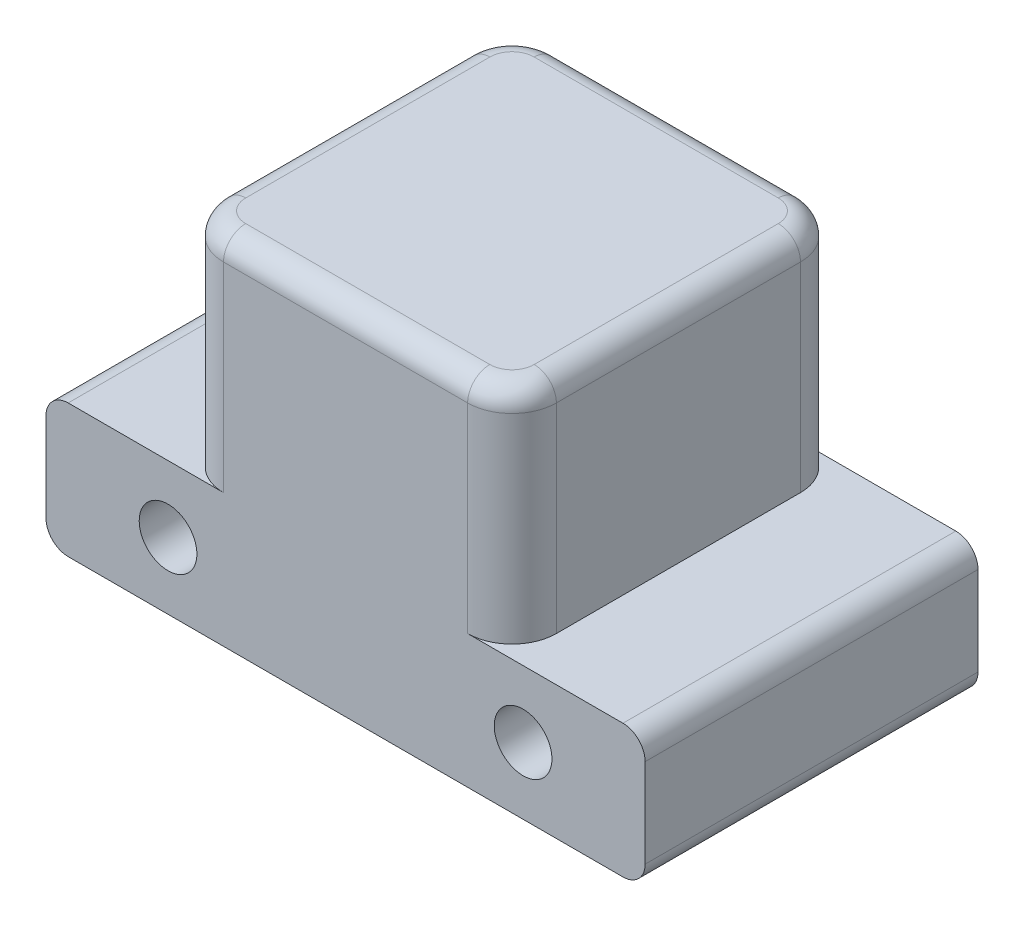
SolidWorks part; units mm, degrees
ref_plane "正面" through (0, 0, 0) normal (0, 0, 1) x (1, 0, 0)
ref_plane "平面" through (0, 0, 0) normal (0, 1, 0) x (1, 0, 0)
ref_plane "右側面" through (0, 0, 0) normal (1, 0, 0) x (0, 0, -1)
sketch "ｽｹｯﾁ1" plane through (0, 0, 0) normal (0, 0, 1) x (1, 0, 0)
  line L0 (0, 8) -> (0, 0) construction
  line L1 (-7.5, 8) -> (7.5, 8)
  line L2 (-7.5, 8) -> (-7.5, -2)
  line L3 (-7.5, -8) -> (7.5, -8)
  line L4 (7.5, 8) -> (7.5, -2)
  line L5 (-7.5, 8) -> (7.5, -8) construction
  line L6 (-7.5, -8) -> (7.5, 8) construction
  line L7 (7.5, -8) -> (13.5, -8)
  line L8 (7.5, -8) -> (7.5, -2) construction
  line L9 (7.5, -2) -> (13.5, -2)
  line L10 (13.5, -8) -> (13.5, -2)
  line L11 (-13.5, -8) -> (-13.5, -2)
  line L12 (-7.5, -2) -> (-13.5, -2)
  line L13 (-7.5, -8) -> (-7.5, -2) construction
  line L14 (-7.5, -8) -> (-13.5, -8)
  line L15 (-7.5, -2) -> (-7.5, -8) construction
  line L16 (7.5, -2) -> (7.5, -8) construction
  circle A0 centre (8, -5) radius 1.3
  circle A1 centre (-8, -5) radius 1.3
  point P0 (0, 0)
  dimension "D5" = 2.6
  dimension "D1" = 15
  dimension "D2" = 10
  dimension "D3" = 6
  dimension "D4" = 6
  dimension "D6" = 3
  dimension "D7" = 16
extrude "ﾎﾞｽ - 押し出し1" add sketch "ｽｹｯﾁ1" along normal blind 15
fillet "ﾌｨﾚｯﾄ1" radius 2 4 edges at (-7.5, 3, 0) (7.5, 3, 0) (7.5, 3, 15) (-7.5, 3, 15)
fillet "ﾌｨﾚｯﾄ3" radius 1 4 edges at (13.5, -8, 7.5) (13.5, -2, 7.5) (-13.5, -8, 7.5) (-13.5, -2, 7.5)
fillet "ﾌｨﾚｯﾄ4" radius 1 8 edges at (6.9142, 8, 14.4142) (7.5, 8, 7.5) (6.9142, 8, 0.5858) (0, 8, 0) (-6.9142, 8, 0.5858) (-7.5, 8, 7.5) (-6.9142, 8, 14.4142) (0, 8, 15)
ref_plane "平面1" through (0, 7, 0) normal (0, 1, 0) x (1, 0, 0)
sketch "ｽｹｯﾁ2" plane through (0, 7, 0) normal (0, 1, 0) x (1, 0, 0)
  line L0 (0, 0) -> (0, -15) construction
  line L1 (5.5, -15) -> (-5.5, -15) construction
  line L3 (-4.15, -3.35) -> (4.15, -3.35)
  line L4 (-4.15, -3.35) -> (-4.15, -11.65)
  line L5 (-4.15, -11.65) -> (4.15, -11.65)
  line L6 (4.15, -3.35) -> (4.15, -11.65)
  line L7 (-4.15, -3.35) -> (4.15, -11.65) construction
  line L8 (-4.15, -11.65) -> (4.15, -3.35) construction
  circle A1 centre (4.15, -3.35) radius 1
  circle A2 centre (4.15, -11.65) radius 1
  circle A3 centre (-4.15, -11.65) radius 1
  circle A4 centre (-4.15, -3.35) radius 1
  point P5 (0, -7.5)
  point P19 (0, -7.5)
  dimension "D1" = 8.3
  dimension "D2" = 2
  dimension "D3" = 4
extrude "ｶｯﾄ - 押し出し1" [suppressed] cut sketch "ｽｹｯﾁ2" against normal blind 2 contours L4 A3 L5 | L5 A2 L6 | L6 A1 L3 | L3 A4 L4 | A4 L4 A3 L5 A2 L6 A1 L3 | L4 A4 L3 | L3 A1 L6 | L6 A2 L5 | L5 A3 L4
sketch "ｽｹｯﾁ3" plane through (0, 7, 0) normal (0, 1, 0) x (1, 0, 0)
  line L0 (0, 0) -> (0, -15) construction
  line L1 (5.5, -15) -> (-5.5, -15) construction
  circle A0 centre (0, -7.5) radius 3.15
  dimension "D1" = 6.3
extrude "ｶｯﾄ - 押し出し2" cut sketch "ｽｹｯﾁ3" against normal blind 2.8
